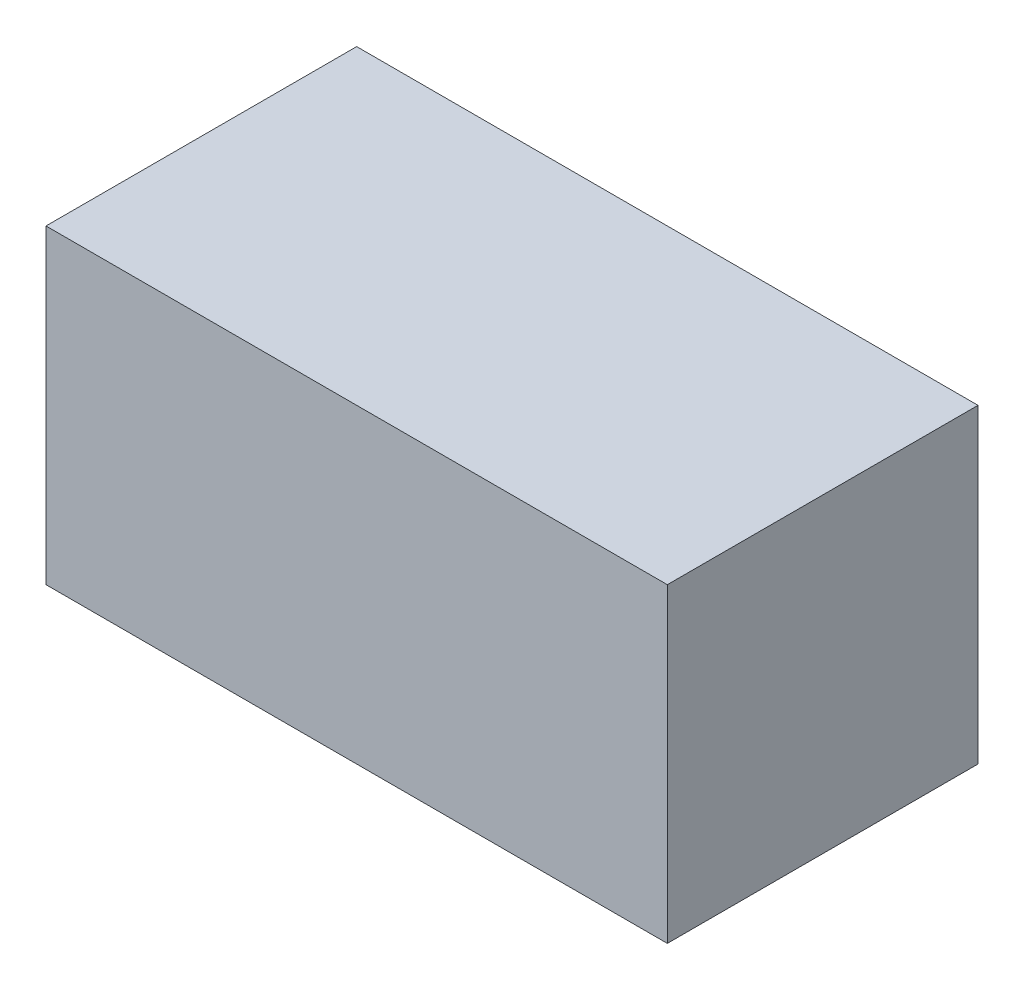
SolidWorks part; units mm, degrees
ref_plane "前视基准面" through (0, 0, 0) normal (0, 0, 1) x (1, 0, 0)
ref_plane "上视基准面" through (0, 0, 0) normal (0, 1, 0) x (1, 0, 0)
ref_plane "右视基准面" through (0, 0, 0) normal (1, 0, 0) x (0, 0, -1)
sketch "草图1" plane through (0, 0, 0) normal (0, 0, 1) x (1, 0, 0)
  line L7 (-0.05, -0.7) -> (1.95, -0.7)
  line L8 (-0.05, -0.7) -> (-0.05, -1.7)
  line L9 (-0.05, -1.7) -> (1.95, -1.7)
  line L10 (1.95, -0.7) -> (1.95, -1.7)
  point P0 (0, 0)
  point P6 (0, 0)
  dimension "D1" = 1
  dimension "D2" = 2
extrude "凸台-拉伸1" add sketch "草图1" along normal blind 1
